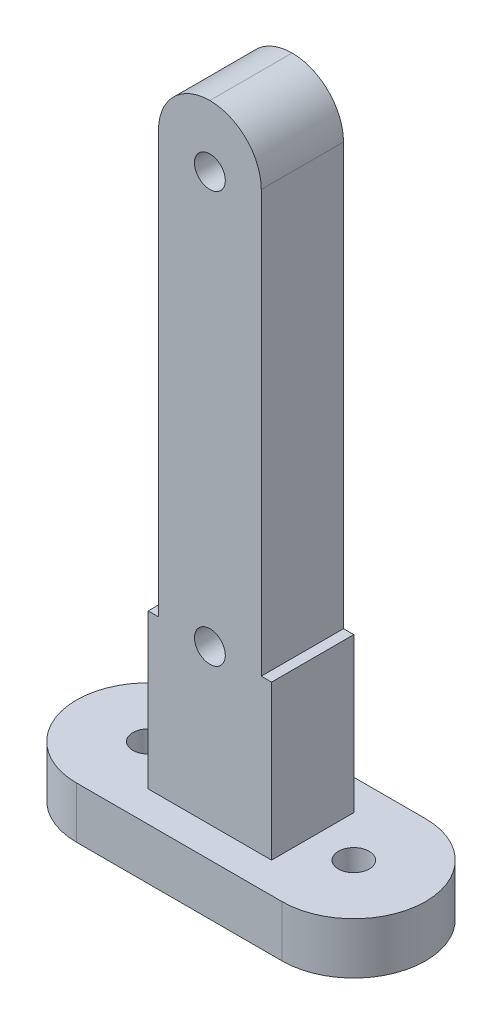
SolidWorks part; units mm, degrees
ref_plane "Front Plane" through (0, 0, 0) normal (0, 0, 1) x (1, 0, 0)
ref_plane "Top Plane" through (0, 0, 0) normal (0, 1, 0) x (1, 0, 0)
ref_plane "Right Plane" through (0, 0, 0) normal (1, 0, 0) x (0, 0, -1)
sketch "Sketch1" plane through (0, 0, 0) normal (0, 1, 0) x (1, 0, 0)
  line L0 (0, 0) -> (-10, 0) construction
  line L1 (0, 0) -> (10, 0) construction
  line L2 (-10, 0) -> (10, 0) construction
  line L3 (-10, 6.9829) -> (10, 6.9829)
  line L4 (-10, -6.9829) -> (10, -6.9829)
  circle A0 centre (-10, 0) radius 1.5
  circle A1 centre (10, 0) radius 1.5
  arc A2 (-10, 6.9829) -> (-10, -6.9829) centre (-10, 0) ccw
  arc A3 (10, -6.9829) -> (10, 6.9829) centre (10, 0) ccw
  point P6 (0, 0)
  dimension "D1" = 10
  dimension "D2" = 10
extrude "Boss-Extrude1" add sketch "Sketch1" along normal blind 5 contours A0 | A1 | L4 A3 L3 A2 region at (-10, 0, 0) region at (10, 0, 0)
sketch "Sketch3" plane through (0, 5, 0) normal (0, 1, 0) x (1, 0, 0)
  line L0 (0, 6.9829) -> (0, -6.9829) construction
  line L1 (-10, 6.9829) -> (10, 6.9829) construction
  line L2 (-10, -6.9829) -> (10, -6.9829) construction
  line L3 (0, 0) -> (-6, 0) construction
  line L4 (-6, 0) -> (-6, -4) construction
  line L5 (0, 0) -> (6, 0) construction
  line L6 (6, 0) -> (6, 4) construction
  line L8 (-6, -4) -> (6, -4)
  line L9 (-6, -4) -> (-6, 4)
  line L10 (-6, 4) -> (6, 4)
  line L11 (6, -4) -> (6, 4)
  dimension "D1" = 6
  dimension "D2" = 4
  dimension "D3" = 6
  dimension "D4" = 4
extrude "Boss-Extrude3" add sketch "Sketch3" along normal blind 15 contours L9 L8 L11 L10
sketch "Sketch4" plane through (0, 0, 4) normal (0, 0, 1) x (1, 0, 0)
  line L0 (0, 20) -> (0, 60) construction
  line L1 (-6, 20) -> (6, 20) construction
  line L2 (0, 20) -> (0, 15.6245) construction
  line L3 (0, 15.6245) -> (-5, 15.6245) construction
  line L4 (0, 60) -> (0, 66) construction
  line L5 (0, 66) -> (5, 66) construction
  line L7 (-5, 15.6245) -> (5, 15.6245)
  line L8 (-5, 15.6245) -> (-5, 66)
  line L9 (-5, 66) -> (5, 66)
  line L10 (5, 15.6245) -> (5, 66)
  circle A0 centre (0, 20) radius 1.5
  circle A1 centre (0, 60) radius 1.5
  dimension "D1" = 40
  dimension "D2" = 6
  dimension "D3" = 5
  dimension "D4" = 5
extrude "Boss-Extrude4" add sketch "Sketch4" against normal up to vertex (8 mm away) contours L8 L7 L10 L9 | A0 | A1 up to point (-6, 20, -4)
fillet "Fillet1" radius 5 2 edges at (-5, 66, 0) (5, 66, 0)
sketch "Sketch5" plane through (0, 0, 4) normal (0, 0, 1) x (1, 0, 0)
  line L0 (-1.5, 20) -> (1.5, 20) construction
  circle A0 centre (0, 20) radius 1.5
extrude "Cut-Extrude1" cut sketch "Sketch5" against normal blind 8
